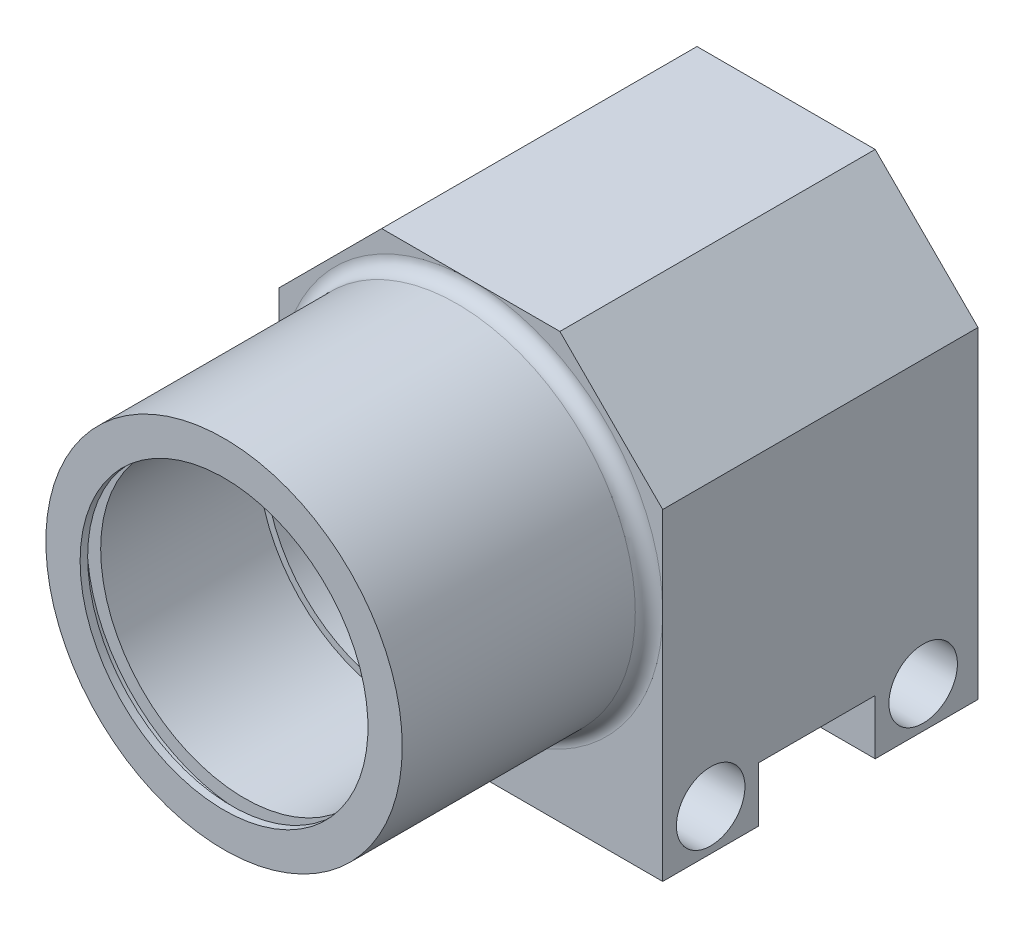
SolidWorks part; units mm, degrees
material "1060 合金"
ref_plane "前视基准面" through (0, 0, 0) normal (0, 0, 1) x (1, 0, 0)
ref_plane "上视基准面" through (0, 0, 0) normal (0, 1, 0) x (1, 0, 0)
ref_plane "右视基准面" through (0, 0, 0) normal (1, 0, 0) x (0, 0, -1)
sketch "草图1" plane through (0, 0, 0) normal (0, 0, 1) x (1, 0, 0)
  line L0 (0, -34) -> (0, 33.0223) construction
  line L1 (-28, -34) -> (28, -34)
  line L2 (-28, -34) -> (-28, 28)
  line L3 (-28, 28) -> (28, 28)
  line L4 (28, -34) -> (28, 28)
  line L5 (0, 0) -> (56.6994, 0) construction
  circle A0 centre (0, 0) radius 24 construction
  point P9 (0, 24)
  point P10 (0, -24)
  point P12 (24, 0)
  dimension "D1" = 10
  dimension "D2" = 48
  dimension "D3" = 4
  dimension "D4" = 4
extrude "凸台-拉伸1" add sketch "草图1" along normal blind 82
sketch "草图3" plane through (0, 0, 0) normal (1, 0, 0) x (0, 0, -1)
  line L0 (5.7193, 0) -> (-112.2198, 0) construction
  line L1 (0, -34) -> (0, 28) construction
  line L2 (-82, 0) -> (0, 0)
  line L3 (-82, 28) -> (-82, -34) construction
  line L4 (-82, 21) -> (-56, 21)
  line L5 (0, 0) -> (0, 23)
  line L7 (-52, 23) -> (0, 23)
  line L9 (-56, 21) -> (-56, 20)
  line L10 (-56, 20) -> (-52, 20)
  line L11 (-52, 23) -> (-52, 20)
  line L12 (-82, 0) -> (-82, 21)
  dimension "D1" = 20
  dimension "D2" = 21
  dimension "D3" = 4
  dimension "D4" = 23
  dimension "D5" = 26
revolve "切除-旋转2" cut sketch "草图3" angle 360 about L0
sketch "草图4" plane through (0, 0, 82) normal (0, 0, 1) x (1, 0, 0)
  line L0 (28, 28) -> (-28, 28) construction
  line L1 (-28, 28) -> (-28, -34) construction
  line L2 (-28, -34) -> (28, -34) construction
  line L3 (28, -34) -> (28, 28) construction
  line L4 (28, 28) -> (-28, 28)
  line L5 (-28, 28) -> (-28, -34)
  line L6 (-28, -34) -> (28, -34)
  line L7 (28, -34) -> (28, 28)
  circle A2 centre (0, 0) radius 26
  dimension "D1" = 52
chamfer "倒角1" distance 15 angle 45 2 edges at (28, 28, 41) (-28, 28, 41)
extrude "切除-拉伸1" cut sketch "草图4" against normal blind 36
hole_wizard "M4 螺纹孔1" positions "草图12" profile "草图11" tap size "M4" standard "GB"
sketch "草图12" plane through (0, 0, 0) normal (0, 0, -1) x (-1, 0, 0)
  line L0 (0, 0) -> (0, 40.8365) construction
  line L6 (28, 13) -> (28, -34) construction
  line L11 (0, 0) -> (18.3848, 18.3848) construction
  circle A3 centre (0, 0) radius 26
  circle A4 centre (0, 0) radius 26 construction
  point P0 (18.3848, 18.3848)
  point P89 (19.0919, -19.0919)
  point P90 (-18.3848, -19.799)
  point P91 (-19.0919, 17.6777)
  dimension "D1" = 45
  dimension "D2" = 9.6152
  dimension "D4" = 4
  dimension "D3" = 3
sketch "草图11" plane through (-18.3848, 18.3848, 0) normal (1, 0, 0) x (0, 1, 0)
  line L0 (0, 0) -> (0, 11.0914)
  line L1 (0, 11.0914) -> (1.65, 10.1)
  line L2 (1.65, 10.1) -> (1.65, 0)
  line L5 (1.65, 0) -> (0, 0)
  line L10 (0, 11.0914) -> (-1.65, 10.1) construction
  line L11 (0, -6.35) -> (0, 107.95) construction
  dimension "螺纹孔钻头直径" = 3.3
  dimension "螺纹孔钻头深度" = 10.1
  dimension "导头角度" = 118
cosmetic thread "孔螺蚊线5" parameters "D1"=8, "D2"=4
cosmetic thread "孔螺蚊线6" parameters "D1"=8, "D2"=4
cosmetic thread "孔螺蚊线7" parameters "D1"=8, "D2"=4
cosmetic thread "孔螺蚊线8" parameters "D1"=8, "D2"=4
sketch "草图13" plane through (28, 0, 0) normal (1, 0, 0) x (0, 0, -1)
  line L0 (-46, -34) -> (0, -34) construction
  line L1 (-46, -34) -> (-46, 13) construction
  circle A0 centre (-39, -28) radius 3.5
  circle A1 centre (-8, -28) radius 3.5
  dimension "D1" = 7
  dimension "D2" = 6
  dimension "D3" = 7
  dimension "D4" = 31
extrude "减震座孔" cut sketch "草图13" against normal through all
sketch "草图14" plane through (28, 0, 0) normal (1, 0, 0) x (0, 0, -1)
  circle A8 centre (-8, -28) radius 5
  circle A9 centre (-39, -28) radius 5
  dimension "D1" = 10
extrude "减震孔" cut sketch "草图14" against normal blind 9.5
mirror "镜向1" about plane through (0, 0, 0) normal (1, 0, 0) of "减震孔"
sketch "草图15" plane through (0, 0, 0) normal (0, 1, 0) x (1, 0, 0)
  line L0 (0, 0) -> (0, -98.0138) construction
  line L1 (-26, -82) -> (26, -82) construction
  line L2 (0, -80.9) -> (-23, -80.9)
  line L3 (0, -80.9) -> (0, -79)
  line L4 (0, -79) -> (-23, -79)
  line L5 (-23, -80.9) -> (-23, -79)
  dimension "D1" = 23
  dimension "D2" = 3
  dimension "D3" = 1.9
revolve "切除-旋转3" cut sketch "草图15" angle 360 about L0
fillet "圆角1" radius 2 1 edges at (26, 0, 46)
chamfer "倒角2" distance 1 angle 45 1 edges at (-23, 0, 0)
sketch "草图16" plane through (28, 0, 0) normal (1, 0, 0) x (0, 0, -1)
  line L0 (-46, -34) -> (0, -34) construction
  line L1 (-32, -34) -> (-15, -34)
  line L2 (-32, -34) -> (-32, -26)
  line L3 (-32, -26) -> (-15, -26)
  line L4 (-15, -34) -> (-15, -26)
  line L5 (-52, -23) -> (-1, -23) construction
  circle A0 centre (-39, -28) radius 3.5 construction
  circle A1 centre (-8, -28) radius 5 construction
  dimension "D1" = 3
  dimension "D2" = 7
  dimension "D3" = 7
extrude "减重坑" cut sketch "草图16" against normal through all
